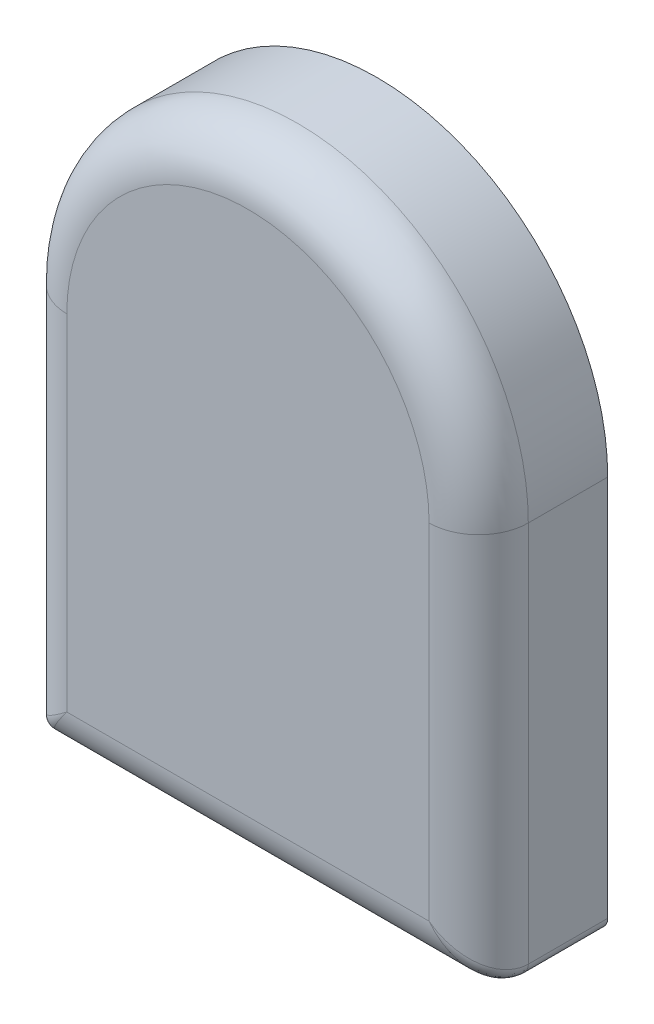
SolidWorks part; units mm, degrees
ref_plane "前视基准面" through (0, 0, 0) normal (0, 0, 1) x (1, 0, 0)
ref_plane "上视基准面" through (0, 0, 0) normal (0, 1, 0) x (1, 0, 0)
ref_plane "右视基准面" through (0, 0, 0) normal (1, 0, 0) x (0, 0, -1)
other "Configuration Table"
sketch "草图1" plane through (0, 0, 0) normal (0, 0, 1) x (1, 0, 0)
  line L0 (8.8, -12.6) -> (-8.8, -12.6)
  line L1 (-9.3, -12.1) -> (-9.3, 3.3)
  line L2 (9.3, 3.3) -> (9.3, -12.1)
  arc A0 (8.8, -12.6) -> (9.3, -12.1) centre (8.8, -12.1) ccw
  arc A1 (-9.3, -12.1) -> (-8.8, -12.6) centre (-8.8, -12.1) ccw
  arc A2 (9.3, 3.3) -> (-9.3, 3.3) centre (0, 3.3) ccw
extrude "凸台-拉伸1" add sketch "草图1" along normal blind 5.2
fillet "圆角1" radius 2 6 edges at (9.1536, -12.4536, 5.2) (9.3, -4.4, 5.2) (0, 12.6, 5.2) (-9.3, -4.4, 5.2) (-9.1536, -12.4536, 5.2) (0, -12.6, 5.2)
